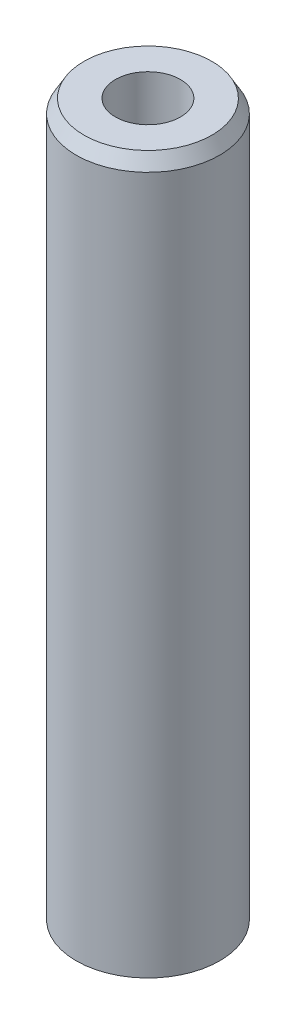
SolidWorks part; units mm, degrees
ref_plane "Front Plane" through (0, 0, 0) normal (0, 0, 1) x (1, 0, 0)
ref_plane "Top Plane" through (0, 0, 0) normal (0, 1, 0) x (1, 0, 0)
ref_plane "Right Plane" through (0, 0, 0) normal (1, 0, 0) x (0, 0, -1)
sketch "Sketch1" plane through (0, 0, 0) normal (0, 1, 0) x (1, 0, 0)
  circle A0 centre (0, 0) radius 5
  dimension "SHAFT_OD" = 10
extrude "Boss-Extrude1" add sketch "Sketch1" along normal blind 50.102
sketch "Sketch2" plane through (0, 0, 0) normal (0, 1, 0) x (1, 0, 0)
  circle A0 centre (0, 0) radius 2.2661
  dimension "BORE_D" = 4.5321
extrude "Cut-Extrude1" cut sketch "Sketch2" along normal through all
chamfer "Chamfer1" distance 0.9381 angle 30 2 edges at (0, 50.102, 5) (0, 0, 5) first distance on face at (0, 50.102, 5) first distance on face at (0, 0, 2.2661)
